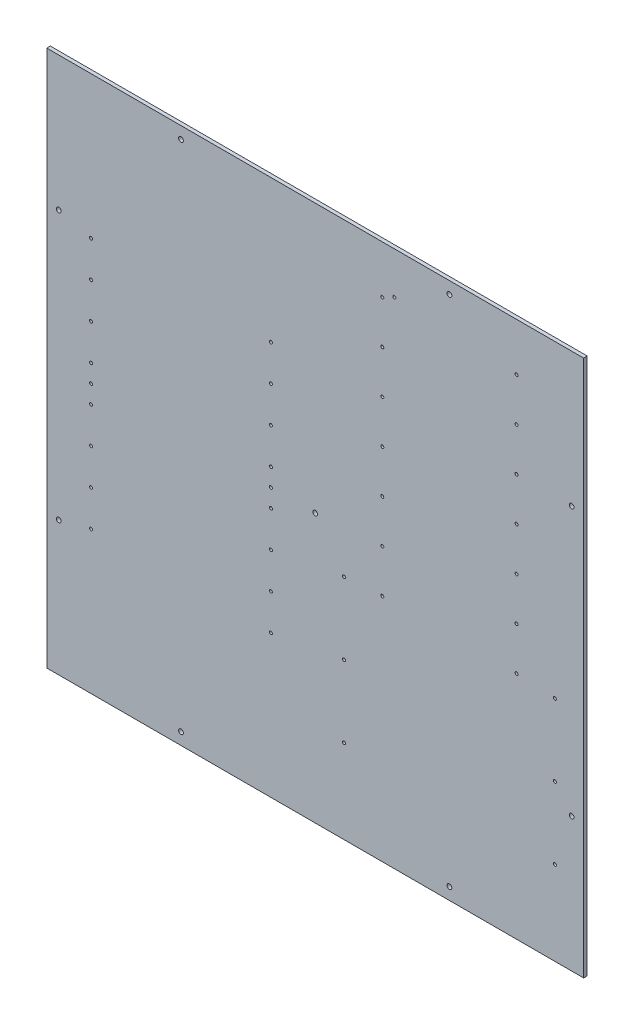
SolidWorks part; units mm, degrees
material "6061-T6 (SS)"
ref_plane "Piano frontale" through (0, 0, 0) normal (0, 0, 1) x (1, 0, 0)
ref_plane "Piano superiore" through (0, 0, 0) normal (0, 1, 0) x (1, 0, 0)
ref_plane "Piano destro" through (0, 0, 0) normal (1, 0, 0) x (0, 0, -1)
sketch "Schizzo1" plane through (0, 0, 0) normal (0, 0, 1) x (1, 0, 0)
  line L0 (10, 448) -> (10, -28.2593) construction
  line L1 (0, 0) -> (448, 0)
  line L2 (0, 0) -> (0, 448)
  line L3 (0, 448) -> (448, 448)
  line L4 (448, 0) -> (448, 448)
  line L6 (224, 448) -> (224, 0) construction
  line L7 (438, 448) -> (438, -28.2593) construction
  line L8 (0, 438) -> (525.0128, 438) construction
  line L9 (0, 10) -> (525.0128, 10) construction
  line L10 (0, 448) -> (0, 224) construction
  line L11 (0, 448) -> (0, 224) construction
  line L15 (0, 336) -> (224, 336) construction
  line L25 (112, 448) -> (112, 224) construction
  line L41 (280, 457.4164) -> (280, -41.798) construction
  line L42 (392, 457.4164) -> (392, -41.798) construction
  line L43 (204.2813, 100) -> (482.2381, 100) construction
  line L44 (183.4892, 70) -> (499.6284, 70) construction
  line L45 (248, -38.4576) -> (248, 170.1585) construction
  line L47 (424, -38.4576) -> (424, 170.1585) construction
  line L58 (336, 27.7675) -> (336, 161.4481) construction
  circle A0 centre (10, 336) radius 2
  circle A1 centre (336, 438) radius 2
  circle A2 centre (438, 336) radius 2
  circle A3 centre (438, 112) radius 2
  circle A4 centre (336, 10) radius 2
  circle A5 centre (112, 10) radius 2
  circle A6 centre (10, 112) radius 2
  circle A7 centre (36.9588, 224) radius 1.25
  circle A8 centre (112, 438) radius 2
  circle A9 centre (36.9588, 239) radius 1.25
  circle A11 centre (36.9588, 269) radius 1.25
  circle A13 centre (36.9588, 299) radius 1.25
  circle A15 centre (36.9588, 329) radius 1.25
  circle A16 centre (248, 70) radius 1.25
  circle A17 centre (248, 130) radius 1.25
  circle A18 centre (424, 130) radius 1.25
  circle A19 centre (424, 70) radius 1.25
  circle A20 centre (290, 413) radius 1.25
  circle A21 centre (280, 408) radius 1.25
  circle A22 centre (392, 408) radius 1.25
  circle A25 centre (280, 372) radius 1.25
  circle A26 centre (392, 372) radius 1.25
  circle A29 centre (280, 336) radius 1.25
  circle A30 centre (392, 336) radius 1.25
  circle A33 centre (280, 300) radius 1.25
  circle A34 centre (392, 300) radius 1.25
  circle A37 centre (280, 264) radius 1.25
  circle A38 centre (392, 264) radius 1.25
  circle A41 centre (280, 228) radius 1.25
  circle A42 centre (392, 228) radius 1.25
  circle A45 centre (280, 192) radius 1.25
  circle A46 centre (392, 192) radius 1.25
  circle A48 centre (36.9588, 119) radius 1.25
  circle A50 centre (36.9588, 149) radius 1.25
  circle A52 centre (36.9588, 179) radius 1.25
  circle A54 centre (36.9588, 209) radius 1.25
  circle A55 centre (187.0412, 209) radius 1.25
  circle A57 centre (187.0412, 179) radius 1.25
  circle A59 centre (187.0412, 149) radius 1.25
  circle A61 centre (187.0412, 119) radius 1.25
  circle A62 centre (187.0412, 329) radius 1.25
  circle A64 centre (187.0412, 299) radius 1.25
  circle A66 centre (187.0412, 269) radius 1.25
  circle A68 centre (187.0412, 239) radius 1.25
  circle A69 centre (187.0412, 224) radius 1.25
  circle A70 centre (224, 224) radius 2
  circle A71 centre (424, 190) radius 1.25
  circle A72 centre (248, 190) radius 1.25
  circle A73 centre (36.9588, 314) radius 1.25 [skipped]
  circle A74 centre (36.9588, 284) radius 1.25 [skipped]
  circle A75 centre (36.9588, 254) radius 1.25 [skipped]
  circle A76 centre (290, 377) radius 1.25 [skipped]
  circle A77 centre (290, 341) radius 1.25 [skipped]
  circle A78 centre (290, 305) radius 1.25 [skipped]
  circle A79 centre (290, 269) radius 1.25 [skipped]
  circle A80 centre (290, 233) radius 1.25 [skipped]
  circle A81 centre (290, 197) radius 1.25 [skipped]
  point P33 (36.9588, 224)
  point P49 (112, 438)
  point P82 (253.9707, 256)
  point P89 (253.9707, 224)
  point P96 (253.9707, 192)
  point P103 (253.9707, 384)
  point P110 (253.9707, 352)
  point P117 (253.9707, 320)
  point P141 (253.9707, 288)
  point P148 (253.9707, 160)
  point P155 (253.9707, 128)
  point P162 (253.9707, 96)
  point P169 (253.9707, 64)
  point P179 (280.1758, 232.4048)
  point P193 (280.1085, 282.4047)
  point P207 (280.0413, 332.4047)
  dimension "D5" = 30
  dimension "D14" = 100
  dimension "D18" = 7
  dimension "D16" = 2.5
  dimension "D17" = 2.5
  dimension "D9" = 4
  dimension "D10" = 2.5
  dimension "D20" = 4
  dimension "D1" = 448
  dimension "D2" = 448
  dimension "D3" = 10
  dimension "D4" = 10
  dimension "D6" = 25
  dimension "D7" = 112
  dimension "D8" = 112
  dimension "D13" = 30
  dimension "D15" = 88
  dimension "D19" = 8
extrude "Estrusione-Estrusione1" add sketch "Schizzo1" against normal blind 3
